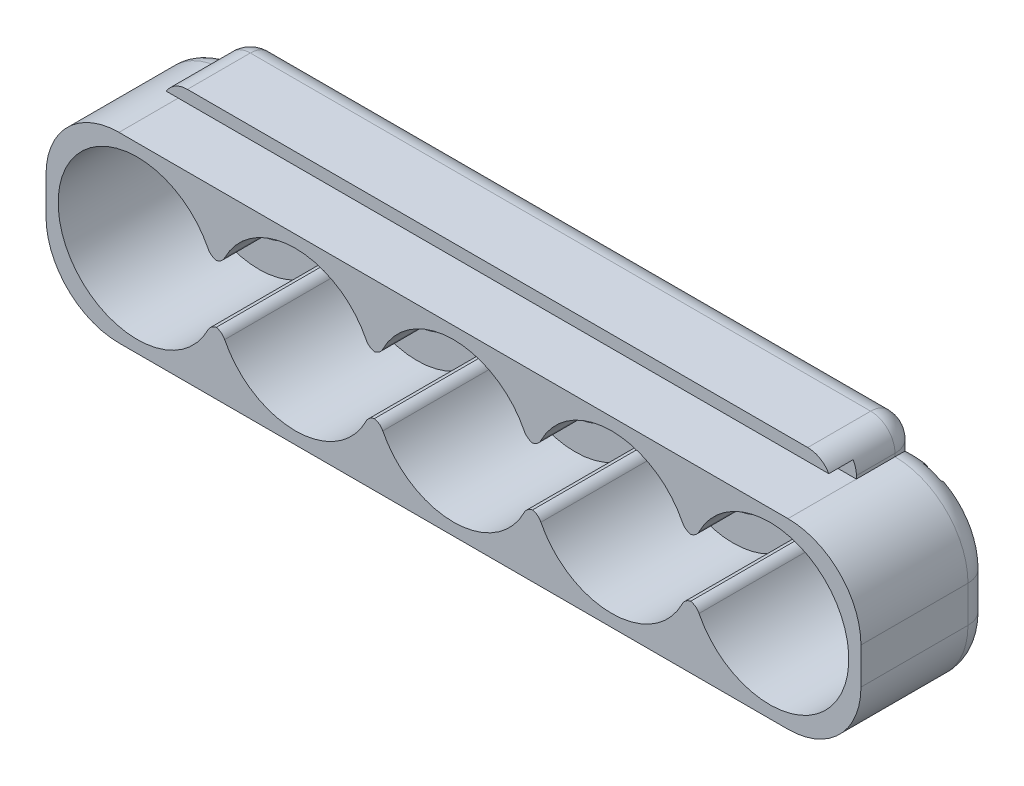
SolidWorks part; units mm, degrees
ref_plane "Front" through (0, 0, 0) normal (0, 0, 1) x (1, 0, 0)
ref_plane "Top" through (0, 0, 0) normal (0, 1, 0) x (1, 0, 0)
ref_plane "Right" through (0, 0, 0) normal (1, 0, 0) x (0, 0, -1)
sketch "Sketch1" plane through (0, 0, 0) normal (0, 0, 1) x (1, 0, 0)
  line L0 (0, 0) -> (13, 0) construction
  line L1 (0, -6.5) -> (52, -6.5) construction
  line L2 (39, 6.5) -> (39, -6.5) construction
  line L3 (-1.5, -7.5) -> (53.5, -7.5)
  line L4 (-7.5, -1.5) -> (-7.5, 1.5)
  line L5 (-1.5, 7.5) -> (53.5, 7.5)
  line L6 (59.5, -1.5) -> (59.5, 1.5)
  line L7 (-7.5, -7.5) -> (59.5, 7.5) construction
  line L8 (-7.5, 7.5) -> (59.5, -7.5) construction
  line L9 (-6.5, 0) -> (58.5, 0) construction
  line L10 (-6.5, 0) -> (-6.5, -7.5) construction
  line L11 (6.0564, 2.36) -> (6.9436, 2.36)
  line L12 (6.0564, -2.36) -> (6.9436, -2.36)
  line L13 (6.5, 7.5) -> (6.5, -7.5) construction
  line L14 (32.9436, -2.36) -> (32.0564, -2.36)
  line L15 (32.9436, 2.36) -> (32.0564, 2.36)
  line L16 (13, 7.5) -> (13, -6.5) construction
  line L17 (19.9436, -2.36) -> (19.0564, -2.36)
  line L18 (19.9436, 2.36) -> (19.0564, 2.36)
  line L19 (45.0564, -2.36) -> (45.9436, -2.36)
  line L20 (45.0564, 2.36) -> (45.9436, 2.36)
  arc A0 (6.0564, 2.36) -> (6.0564, -2.36) centre (0, 0) ccw
  arc A8 (53.5, 7.5) -> (59.5, 1.5) centre (53.5, 1.5) cw
  arc A9 (53.5, -7.5) -> (59.5, -1.5) centre (53.5, -1.5) ccw
  arc A10 (-1.5, -7.5) -> (-7.5, -1.5) centre (-1.5, -1.5) cw
  arc A11 (-7.5, 1.5) -> (-1.5, 7.5) centre (-1.5, 1.5) cw
  arc A12 (6.9436, -2.36) -> (19.0564, -2.36) centre (13, 0) ccw
  arc A13 (32.0564, 2.36) -> (19.9436, 2.36) centre (26, 0) ccw
  arc A14 (32.9436, -2.36) -> (45.0564, -2.36) centre (39, 0) ccw
  arc A15 (19.9436, -2.36) -> (32.0564, -2.36) centre (26, 0) ccw
  arc A16 (19.0564, 2.36) -> (6.9436, 2.36) centre (13, 0) ccw
  arc A17 (45.9436, -2.36) -> (45.9436, 2.36) centre (52, 0) ccw
  arc A18 (45.0564, 2.36) -> (32.9436, 2.36) centre (39, 0) ccw
  point P1 (26, 0)
  point P40 (6.5, 2.36)
  point P41 (6.5, -2.36)
  dimension "D1" = 13
  dimension "D4" = 6
  dimension "D3" = 1
  dimension "D2" = 1
  dimension "D5" = 15
  dimension "D7" = 13
  dimension "D9" = 2.36
  dimension "D6" = 4
extrude "Boss-Extrude1" add sketch "Sketch1" along normal blind 15
sketch "Sketch2" plane through (0, 0, 0) normal (0, 0, -1) x (-1, 0, 0)
  line L0 (-39, 0) -> (-26, 0) construction
  line L1 (-59.5, 0) -> (7.5, 0) construction
  line L2 (-39, 0) -> (-52, 0) construction
  line L4 (-59.5, 1.5) -> (-59.5, -1.5)
  line L5 (-53.5, -7.5) -> (1.5, -7.5)
  line L6 (7.5, -1.5) -> (7.5, 1.5)
  line L7 (1.5, 7.5) -> (-53.5, 7.5)
  line L8 (-59.5, 1.5) -> (-59.5, -1.5)
  line L9 (-53.5, -7.5) -> (1.5, -7.5)
  line L10 (7.5, -1.5) -> (7.5, 1.5)
  line L11 (1.5, 7.5) -> (-53.5, 7.5)
  circle A0 centre (-39, 0) radius 4
  circle A1 centre (-52, 0) radius 4
  circle A2 centre (-26, 0) radius 4
  circle A3 centre (-13, 0) radius 4
  arc A4 (-53.5, 7.5) -> (-59.5, 1.5) centre (-53.5, 1.5) ccw
  arc A5 (-59.5, -1.5) -> (-53.5, -7.5) centre (-53.5, -1.5) ccw
  arc A6 (1.5, -7.5) -> (7.5, -1.5) centre (1.5, -1.5) ccw
  arc A7 (7.5, 1.5) -> (1.5, 7.5) centre (1.5, 1.5) ccw
  arc A8 (-53.5, 7.5) -> (-59.5, 1.5) centre (-53.5, 1.5) ccw
  arc A9 (-59.5, -1.5) -> (-53.5, -7.5) centre (-53.5, -1.5) ccw
  arc A10 (1.5, -7.5) -> (7.5, -1.5) centre (1.5, -1.5) ccw
  arc A11 (7.5, 1.5) -> (1.5, 7.5) centre (1.5, 1.5) ccw
  circle A12 centre (0, 0) radius 4
  circle A13 centre (0, 0) radius 4
  circle A14 centre (-13, 0) radius 4
  circle A15 centre (-26, 0) radius 4
  circle A16 centre (-39, 0) radius 4
  arc A17 (-45.0564, -2.36) -> (-32.9436, -2.36) centre (-39, 0) ccw construction
  arc M10 (-53.5, 7.5) -> (-59.5, 1.5) centre (-53.5, 1.5) ccw
  line M11 (-59.5, 1.5) -> (-59.5, -1.5)
  arc M12 (-59.5, -1.5) -> (-53.5, -7.5) centre (-53.5, -1.5) ccw
  line M13 (-53.5, -7.5) -> (1.5, -7.5)
  arc M14 (1.5, -7.5) -> (7.5, -1.5) centre (1.5, -1.5) ccw
  line M15 (7.5, -1.5) -> (7.5, 1.5)
  arc M16 (7.5, 1.5) -> (1.5, 7.5) centre (1.5, 1.5) ccw
  line M17 (1.5, 7.5) -> (-53.5, 7.5)
  arc M18 (-6.0564, 2.36) -> (-6.0564, -2.36) centre (0, 0) cw
  line M36 (-19.9436, 2.36) -> (-19.0564, 2.36)
  arc M37 (-19.0564, 2.36) -> (-6.9436, 2.36) centre (-13, 0) cw
  line M38 (-6.9436, 2.36) -> (-6.0564, 2.36)
  line M39 (-6.0564, -2.36) -> (-6.9436, -2.36)
  arc M40 (-6.9436, -2.36) -> (-19.0564, -2.36) centre (-13, 0) cw
  line M41 (-19.0564, -2.36) -> (-19.9436, -2.36)
  arc M42 (-19.9436, -2.36) -> (-32.0564, -2.36) centre (-26, 0) cw
  line M43 (-32.0564, -2.36) -> (-32.9436, -2.36)
  arc M44 (-32.9436, -2.36) -> (-45.0564, -2.36) centre (-39, 0) cw
  line M45 (-32.9436, 2.36) -> (-32.0564, 2.36)
  arc M46 (-32.0564, 2.36) -> (-19.9436, 2.36) centre (-26, 0) cw
  dimension "D2" = 8
  dimension "D4" = 13
  dimension "D6" = 13
  dimension "D1" = 0
  dimension "D3" = 4
  dimension "D5" = 2
extrude "Boss-Extrude2" add sketch "Sketch2" along normal blind 0.8 contours M17 M10 M11 M12 M13 M14 M15 M16 M46 M36 M37 M38 M18 M39 M40 M41 M42 M43 M44 M45 | A12 A3 A2 A0 M36 M46 M45 M44 M43 M42 M41 M40 M39 M18 M38 M37
fillet "Fillet1" radius 1 16 edges at (19.0564, 2.36, 7.5) (19.9436, 2.36, 7.5) (32.0564, 2.36, 7.5) (32.0564, -2.36, 7.5) (32.9436, -2.36, 7.5) (19.0564, -2.36, 7.5) (19.9436, -2.36, 7.5) (6.0564, -2.36, 7.5) (6.9436, -2.36, 7.5) (6.0564, 2.36, 7.5) (6.9436, 2.36, 7.5) (45.0564, -2.36, 7.5) (45.9436, -2.36, 7.5) (45.9436, 2.36, 7.5) (45.0564, 2.36, 7.5) (32.9436, 2.36, 7.5)
ref_plane "Plane1" through (53.5, 0, 0) normal (1, 0, 0) x (0, 0, -1)
sketch "Sketch4" plane through (53.5, 0, 0) normal (1, 0, 0) x (0, 0, -1)
  line L0 (-25.5, 7.5) -> (-4.5, 7.5) construction
  line L1 (-4.5, 7.5) -> (-4.5, 8.5) construction
  line L2 (-4.375, 7.5) -> (-4.375, 8.75)
  line L3 (-15, 7.5) -> (0.8, 7.5) construction
  line L4 (-4.375, 8.75) -> (-6.375, 8.75)
  line L5 (-6.375, 8.75) -> (-6.375, 9.75)
  line L6 (-6.375, 9.75) -> (-1.2, 9.75)
  line L7 (0.8, 7.75) -> (0.8, 7.5)
  line L8 (-4.5, 7.5) -> (0.8, 7.5)
  arc A0 (-1.2, 9.75) -> (0.8, 7.75) centre (-1.2, 7.75) cw
  point P2 (-15, 7.5)
  dimension "D7" = 2
  dimension "D1" = 21
  dimension "D2" = 1
  dimension "D3" = 0.25
  dimension "D4" = 2
  dimension "D5" = 1
  dimension "D6" = 1.25
extrude "Boss-Extrude5" add sketch "Sketch4" against normal up to vertex (55 mm away) contours A0 L6 L5 L4 L2 L8 L7 up to point (-1.5, 7.5, -0.8)
fillet "Fillet3" radius 2 13 edges at (-1.5, 7.625, -0.8) (-1.5, 9.1642, -0.2142) (53.5, 7.625, -0.8) (53.5, 9.1642, -0.2142) (-1.5, 9.75, 3.7875) (53.5, 9.75, 3.7875) (-5.7426, 5.7426, -0.8) (-7.5, 0, -0.8) (-5.7426, -5.7426, -0.8) (26, -7.5, -0.8) (57.7426, -5.7426, -0.8) (59.5, 0, -0.8) (57.7426, 5.7426, -0.8)
ref_plane "Plane2" through (0, 0, 10) normal (0, 0, 1) x (1, 0, 0)
other "SurfaceCut1" flip cut yes
sketch "Sketch5" plane through (0, 0, -0.8) normal (0, 0, -1) x (-1, 0, 0)
  line L1 (-52, -0.5) -> (0, -0.5)
  line L2 (-52, -0.5) -> (-52, 0.5)
  line L3 (-52, 0.5) -> (0, 0.5)
  line L4 (0, -0.5) -> (0, 0.5)
  line L5 (-52, -0.5) -> (0, 0.5) construction
  line L6 (-52, 0.5) -> (0, -0.5) construction
  circle A0 centre (-26, 0) radius 4 construction
  point P0 (-26, 0)
  point P5 (0, 0)
  dimension "D1" = 1
extrude "Cut-Extrude1" cut sketch "Sketch5" against normal up to surface (0.8 mm away) up to face at (35, 0, 0)
sketch "Sketch6" plane through (0, 0, -0.8) normal (0, 0, -1) x (-1, 0, 0)
  line L0 (-55.5, 4.9641) -> (-53.5, 1.5) construction
  line L5 (-56.2071, 6.9069) -> (-54.7929, 7.4069)
  line L6 (-56.2071, 6.9069) -> (-54.2071, 1.25)
  line L7 (-54.7929, 7.4069) -> (-52.7929, 1.75)
  line L8 (-54.2071, 1.25) -> (-52.7929, 1.75)
  line L9 (-26, 7.75) -> (-26, -5.5) construction
  line L10 (-0.5, 7.75) -> (-51.5, 7.75) construction
  line L11 (-53.5, -5.5) -> (1.5, -5.5) construction
  line L12 (2.7929, 7.4069) -> (0.7929, 1.75)
  line L13 (2.2071, 1.25) -> (0.7929, 1.75)
  line L14 (4.2071, 6.9069) -> (2.2071, 1.25)
  line L15 (4.2071, 6.9069) -> (2.7929, 7.4069)
  arc A0 (-53.5, 7.5) -> (-59.5, 1.5) centre (-53.5, 1.5) ccw construction
  arc A2 (-51.5, 4.9641) -> (-57.5, 1.5) centre (-53.5, 1.5) ccw construction
  point P12 (-55.5, 7.1569)
  point P15 (-53.5, 1.5)
  dimension "D1" = 1.5
extrude "Cut-Extrude2" cut sketch "Sketch6" against normal up to surface (0.8 mm away) up to face at (26, 0, 0)
fillet "Fillet4" radius 1 22 edges at (48.0314, -0.5, -0.4) (29.9686, -0.5, -0.4) (22.0314, -0.5, -0.4) (16.9686, -0.5, -0.4) (9.0314, -0.5, -0.4) (3.9686, -0.5, -0.4) (42.9686, -0.5, -0.4) (35.0314, -0.5, -0.4) (48.0314, 0.5, -0.4) (22.0314, 0.5, -0.4) (29.9686, 0.5, -0.4) (9.0314, 0.5, -0.4) (16.9686, 0.5, -0.4) (3.9686, 0.5, -0.4) (35.0314, 0.5, -0.4) (42.9686, 0.5, -0.4) (-2.7815, 2.8746, -0.4) (-1.487, 3.7133, -0.4) (-3.0127, 5.7597, 0) (54.7815, 2.8746, -0.4) (53.487, 3.7133, -0.4) (55.0127, 5.7597, 0)
